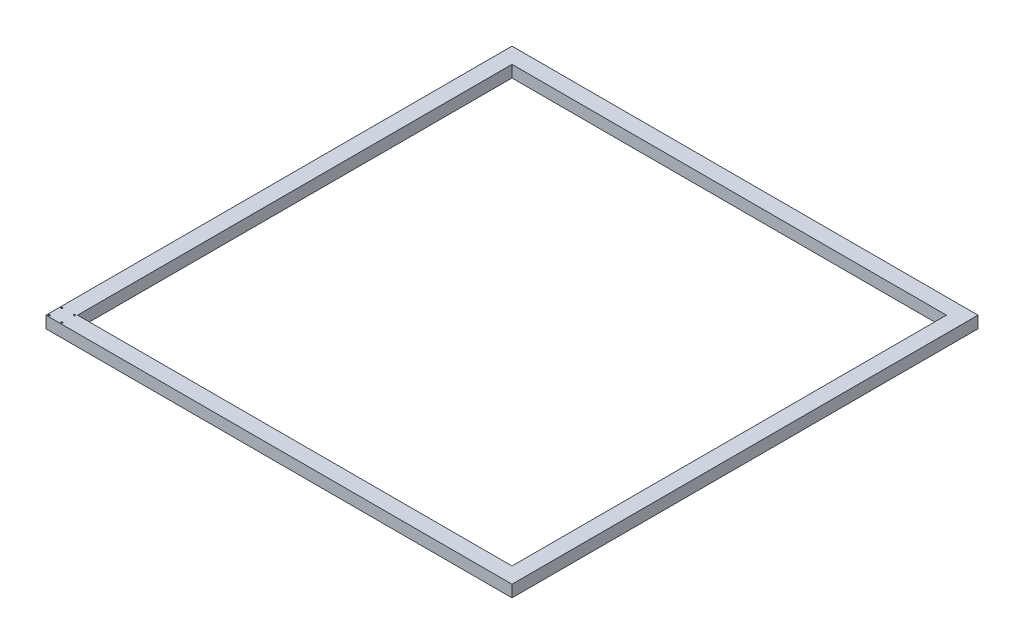
SolidWorks part; units mm, degrees
material "Concreto"
ref_plane "Plano frontal" through (0, 0, 0) normal (0, 0, 1) x (1, 0, 0)
ref_plane "Plano superior" through (0, 0, 0) normal (0, 1, 0) x (1, 0, 0)
ref_plane "Plano direito" through (0, 0, 0) normal (1, 0, 0) x (0, 0, -1)
sketch "Esboço1" plane through (0, 0, 0) normal (0, 1, 0) x (1, 0, 0)
  line L5 (-2750, 2750) -> (2750, 2750)
  line L6 (-2750, 2750) -> (-2750, -2750)
  line L11 (-2750, -2750) -> (2750, -2750)
  line L12 (2750, 2750) -> (2750, -2750)
  line L13 (-2750, 2750) -> (2750, -2750) construction
  line L14 (-2750, -2750) -> (2750, 2750) construction
  line L15 (-2950, 2950) -> (2950, 2950)
  line L16 (-2950, 2950) -> (-2950, -2950)
  line L17 (-2950, -2950) -> (2950, -2950)
  line L18 (2950, 2950) -> (2950, -2950)
  line L19 (-2950, 2950) -> (2950, -2950) construction
  line L20 (-2950, -2950) -> (2950, 2950) construction
  point P0 (0, 0)
  point P6 (0, 0)
  dimension "D1" = 5500
  dimension "D2" = 5500
  dimension "D3" = 200
  dimension "D4" = 200
extrude "Ressalto-extrusão1" add sketch "Esboço1" along normal blind 150
sketch "Esboço6" plane through (0, 150, 0) normal (0, 1, 0) x (1, 0, 0)
  line L4 (-2750, -2950) -> (-2750, -2750)
  line L5 (-2950, -2950) -> (-2750, -2950)
  line L6 (-2950, -2750) -> (-2950, -2950)
  line L7 (-2750, -2750) -> (-2950, -2750)
  line L8 (-2750, -2950) -> (-2750, -2750) construction
  line L9 (-2950, -2950) -> (-2750, -2950) construction
  line L10 (-2950, -2750) -> (-2950, -2950) construction
  line L11 (-2750, -2750) -> (-2950, -2750) construction
  circle A1 centre (-2770, -2770) radius 10
  circle A2 centre (-2770, -2770) radius 10
  circle A3 centre (-2770, -2930) radius 10
  circle A4 centre (-2930, -2930) radius 10
  circle A5 centre (-2930, -2770) radius 10
  point P2 (0, 0)
  point P5 (0, 0)
  dimension "D1" = 0
  dimension "D2" = 0
  dimension "D3" = 2
  dimension "D4" = 2
extrude "Corte-extrusão3" cut sketch "Esboço6" against normal through all
